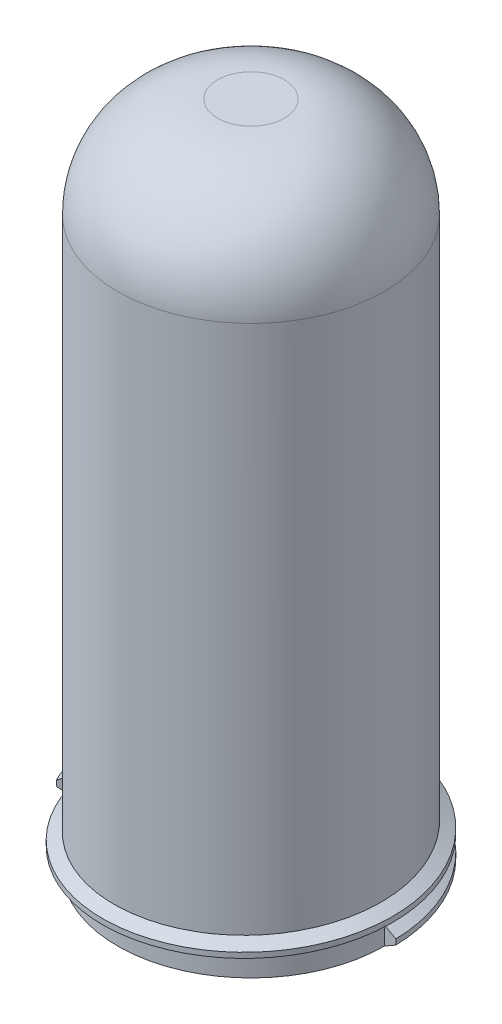
SolidWorks part; units mm, degrees
ref_plane "Front Plane" through (0, 0, 0) normal (0, 0, 1) x (1, 0, 0)
ref_plane "Top Plane" through (0, 0, 0) normal (0, 1, 0) x (1, 0, 0)
ref_plane "Right Plane" through (0, 0, 0) normal (1, 0, 0) x (0, 0, -1)
sketch "Sketch1" plane through (0, 0, 0) normal (0, 1, 0) x (1, 0, 0)
  circle A0 centre (0, 0) radius 4
extrude "Boss-Extrude1" add sketch "Sketch1" along normal blind 20 contours A0
fillet "Fillet1" radius 3 1 edges at (0, 20, 4)
thread "Thread1" pitch 0.635 method extrude profile "Thread Profile3" start angle 0, offset 0, length 1, pitch 0.635, diameter 8
ref_plane "Plane3" through (4, 0, 0) normal (0, 0, -1) x (-1, 0, 0)
sketch "Thread Profile3" plane through (4, 0, 0) normal (0, 0, -1) x (-1, 0, 0)
  line L0 (0, 0) -> (0, 0.635) construction
  line L11 (0, 0) -> (0, 0.5556)
  line L12 (0, 0.5556) -> (-0.3437, 0.3572)
  line L13 (-0.3437, 0.3572) -> (-0.3437, 0.1984)
  line L15 (-0.3437, 0.1984) -> (0, 0)
  line L17 (-0.3437, 0.2778) -> (0, 0.2778) construction
  point P2 (0, 0)
  dimension "Pitch" = 0.635
  dimension "Profile_Angle" = 60
  dimension "Profile_Land" = 0.1588
  dimension "Profile_Height" = 0.3437
sketch "Sketch8" plane through (0, 0, 0) normal (0, -1, 0) x (-1, 0, 0)
  circle A0 centre (0, 0) radius 3.5
extrude "Cut-Extrude1" cut sketch "Sketch8" against normal blind 17.5
fillet "Fillet4" radius 2.5 1 edges at (0, 17.5, -3.5)
